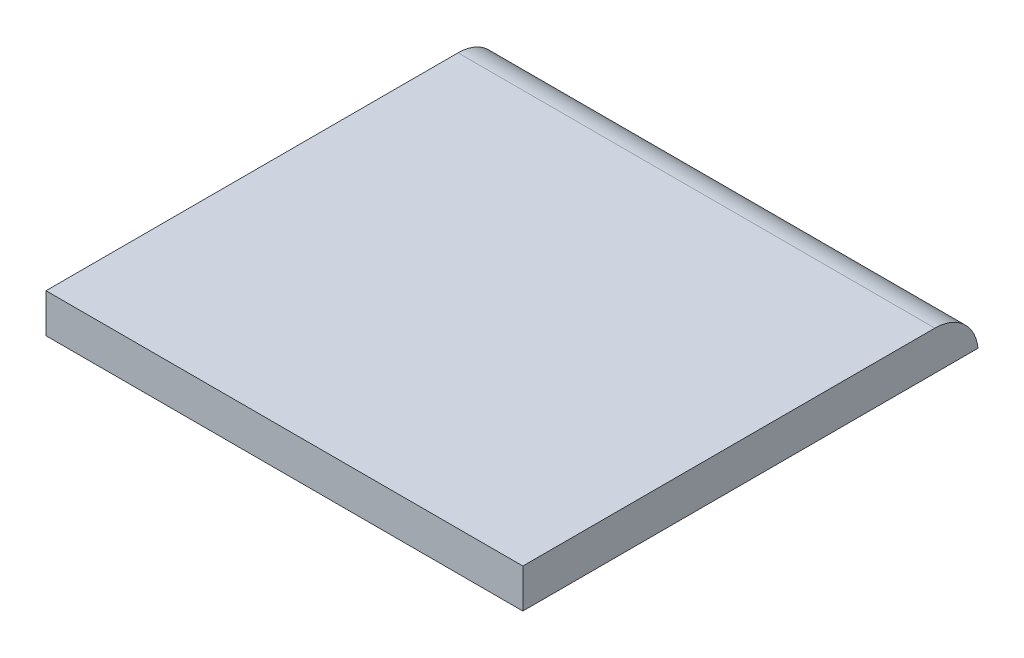
SolidWorks part; units mm, degrees
material "Erable"
ref_plane "Plan de face" through (0, 0, 0) normal (0, 0, 1) x (1, 0, 0)
ref_plane "Plan de dessus" through (0, 0, 0) normal (0, 1, 0) x (1, 0, 0)
ref_plane "Plan de droite" through (0, 0, 0) normal (1, 0, 0) x (0, 0, -1)
sketch "Esquisse1" plane through (0, 0, 0) normal (1, 0, 0) x (0, 0, -1)
  line L1 (0, 0) -> (105, 0)
  line L2 (0, 0) -> (0, 9)
  line L3 (0, 9) -> (105, 9)
  line L4 (105, 0) -> (105, 9)
  dimension "D1" = 105
  dimension "D2" = 9
extrude "Boss.-Extru.1" add sketch "Esquisse1" along normal blind 110
fillet "Congé1" radius 10 1 edges at (55, 9, -105)
